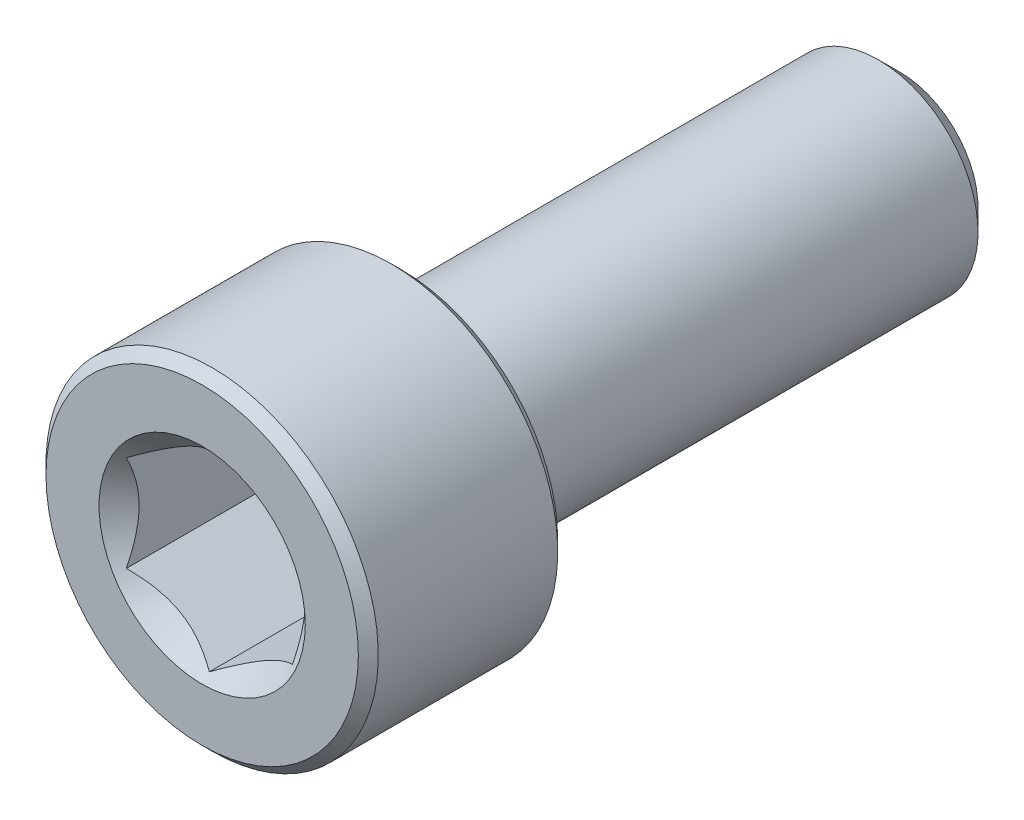
SolidWorks part; units mm, degrees
material "Alloy Steel"
ref_plane "Front Plane" through (0, 0, 0) normal (0, 0, 1) x (1, 0, 0)
ref_plane "Top Plane" through (0, 0, 0) normal (0, 1, 0) x (1, 0, 0)
ref_plane "Right Plane" through (0, 0, 0) normal (1, 0, 0) x (0, 0, -1)
sketch "Sketch1" plane through (0, 0, 0) normal (1, 0, 0) x (0, 0, -1)
  line L0 (-10.5, 0) -> (10.5, 0) construction
  line L1 (10.5, 0) -> (10.5, 2.3505) construction
  line L2 (10.5, 2.3505) -> (9.8505, 3) construction
  line L3 (9.8505, 3) -> (9.75, 3) construction
  line L4 (9.75, 3) -> (-4.5, 3) construction
  line L5 (-4.5, 3) -> (-4.5, 5) construction
  line L6 (-4.5, 5) -> (-10.5, 5) construction
  line L7 (-10.5, 5) -> (-10.5, 0) construction
  line L8 (10.5, 2.3505) -> (10.5, 3) construction
  line L9 (10.4375, 3.1083) -> (10.9375, 2.2422) construction
  line L10 (10.9375, 2.2422) -> (11.4375, 3.1083) construction
  line L11 (11.4375, 3.1083) -> (10.4375, 3.1083) construction
  line L12 (10.9375, 3.1083) -> (10.9375, 3) construction
  line L13 (10.9375, 2.2422) -> (10.9375, 2.3505) construction
  line L14 (10.875, 2.3505) -> (11, 2.3505) construction
  line L15 (10.5, 3) -> (11.375, 3) construction
  line L16 (10.4687, 3.0541) -> (11.4062, 3.0541) construction
  line L17 (10.5, 0) -> (10.5, -3) construction
  line L18 (-4.8, 5) -> (-4.5, 4.7) construction
  line L19 (-10.2, 5) -> (-10.5, 4.7) construction
  line L20 (-4.5, 3) -> (-4.5, 0) construction
  line L21 (-4.5, 1.5) -> (0.5, 1.5) construction
  line L22 (0.5, 1.5) -> (5.5, 1.5) construction
  line L23 (5.5, 1.5) -> (10.5, 1.5) construction
  line L24 (0.5, 1.5) -> (0.5, 3) construction
  line L25 (0.5, 3) -> (0.5, 5) construction
  line L26 (5.5, 1.5) -> (5.5, 5) construction
  point P0 (-10.5, 2.5)
  point P3 (8, 3)
  point P4 (0, 0)
  point P18 (5.5, 3)
  point P22 (10.9375, 2.3505)
  point P24 (9.75, 3)
  point P25 (10.9375, 3)
  point P28 (10.9375, 3.0541)
  point P29 (8, -3)
  point P30 (0.5, 3)
  point P31 (-7.5, 5)
  point P37 (-5.55, 5)
  point P38 (-10.05, 5)
  point P45 (0.5, 1.5)
  point P46 (5.5, 1.5)
  dimension "D2" = 0.125
  dimension "D7" = 0.3
  dimension "D8" = 0.3
  dimension "D9" = 0.3
  dimension "D10" = 0.15
  dimension "D11" = 0.75
  dimension "Drive Size" = 5
  dimension "Head Diameter" = 10
  dimension "Head Height" = 6
  dimension "Thread Pitch" = 1
  dimension "Thread Dia" = 6
  dimension "Length" = 15
  dimension "D12" = 0.75
  dimension "D4" = 2.5
  dimension "D3" = 45
sketch "Sketch2" plane through (0, 0, 0) normal (1, 0, 0) x (0, 0, -1)
  line L0 (-10.5, 0) -> (-10.5, 4.7)
  line L1 (-10.2, 5) -> (-4.8, 5)
  line L2 (-4.5, 4.7) -> (-4.5, 3.3)
  line L4 (9.8505, 3) -> (10.5, 2.3505)
  line L5 (10.5, 2.3505) -> (10.5, 0)
  line L6 (-4.5, 5) -> (-10.5, 5) construction
  line L7 (10.5, 0) -> (-10.5, 0)
  line L8 (-10.2, 5) -> (-10.5, 4.7) construction
  line L10 (-10.2, 5) -> (-10.5, 4.7)
  line L14 (-4.8, 5) -> (-4.5, 4.7) construction
  line L16 (-4.8, 5) -> (-4.5, 4.7)
  line L17 (-4.5, 3) -> (-4.5, 5) construction
  line L19 (-4.2, 3) -> (9.8505, 3)
  line L20 (9.75, 3) -> (-4.5, 3) construction
  arc A1 (-4.5, 3.3) -> (-4.2, 3) centre (-4.2, 3.3) ccw
  dimension "D3" = 0.3
revolve "Revolve1" add sketch "Sketch2" angle 360 about L7
sketch "Sketch3" plane through (0, 0, 10.5) normal (0, 0, 1) x (1, 0, 0)
  line L1 (2.5, -1.4434) -> (2.5, 1.4434)
  line L2 (2.5, 1.4434) -> (0, 2.8868)
  line L3 (0, 2.8868) -> (-2.5, 1.4434)
  line L4 (-2.5, 1.4434) -> (-2.5, -1.4434)
  line L5 (-2.5, -1.4434) -> (0, -2.8868)
  line L6 (0, -2.8868) -> (2.5, -1.4434)
  circle A0 centre (0, 0) radius 2.5 construction
  circle A1 centre (0, 0) radius 5 construction
  circle A2 centre (0, 0) radius 5 construction
  circle A3 centre (0, 0) radius 2.8868 construction
  point P13 (0, 0)
  dimension "D1" = 5.7735
extrude "Cut-Extrude1" cut sketch "Sketch3" against normal offset from surface (5 mm away) 1 up to face at (0, 4.7, 4.5)
sketch "Sketch4" plane through (0, 0, 10.5) normal (0, 0, 1) x (1, 0, 0)
  circle A0 centre (0, 0) radius 3.1033
  dimension "D1" = 6.2065
extrude "Cut-Extrude2" cut sketch "Sketch4" against normal up to vertex (3 mm away) draft 45 up to point (0, 5, 7.5)
sketch "Sketch11" plane through (0, 0, 0) normal (1, 0, 0) x (0, 0, -1)
  line L0 (-10.5, 0) -> (10.5, 0) construction
  line L1 (-10.5, 0) -> (10.5, 0) construction
  line L2 (-1.6875, 0) -> (-1.6875, 3) construction
  line L3 (9.75, 3) -> (-4.5, 3) construction
  line L4 (7.6875, 0) -> (7.6875, 3) construction
  line L6 (10.5, 2.3505) -> (10.5, 3) construction
  point P2 (-1.6875, 0)
  point P3 (7.6875, 0)
  dimension "D1" = 2.8125
  dimension "D2" = 2.8125
sketch "Sketch6" [suppressed] plane through (0, 0, -10.5) normal (0, 0, -1) x (-1, 0, 0)
  circle A0 centre (0, 0) radius 3
curve "Helix/Spiral1" [suppressed] pitch 1 height 16 turns 16
sketch "Sketch10" [suppressed] plane through (0, 0, 0) normal (1, 0, 0) x (0, 0, -1)
  line L0 (-4.2, -5) -> (-4.2, 5)
  line L5 (-10.5, 0) -> (10.5, 0) construction
  line L6 (-4.2, 3) -> (-4.2, -3) construction
  point P3 (-4.2, 0)
split "Split1" [suppressed] bodies to split 106
sketch "Sketch7" [suppressed] plane through (0, 0, 0) normal (1, 0, 0) x (0, 0, -1)
  line L0 (10.4687, 3.0541) -> (11.4062, 3.0541)
  line L1 (11.4062, 3.0541) -> (11, 2.3505)
  line L2 (11, 2.3505) -> (10.875, 2.3505)
  line L3 (10.875, 2.3505) -> (10.4687, 3.0541)
sweep "Cut-Sweep1" [suppressed] cut profiles "Sketch7" path "Helix/Spiral1"
sketch "Sketch8" [suppressed] plane through (0, 0, 0) normal (1, 0, 0) x (0, 0, -1)
  line L0 (-4.5, 0) -> (-4.5, 3)
  line L1 (-4.2, -3) -> (-4.2, 3) construction
  line L2 (-4.5, 3) -> (-4.2, 3)
  line L4 (-4.2, 3) -> (-2.4679, 0)
  line L5 (-2.4679, 0) -> (-4.5, 0)
  line L6 (9.75, 3) -> (-4.5, 3) construction
  line L7 (-10.5, 0) -> (10.5, 0) construction
  dimension "D1" = 60
revolve "Revolve2" [suppressed] add sketch "Sketch8" angle 360 about L5
equation "\"D2@Sketch1\" = \"Thread Pitch@Sketch1\" / 8"
equation "\"D4@Helix/Spiral1\" = \"Thread Pitch@Sketch1\""
equation "\"D7@Sketch1\" = \"Head Height@Sketch1\" * .05"
equation "\"D8@Sketch1\"=\"D7@Sketch1\""
equation "\"D9@Sketch1\"=\"D7@Sketch1\""
equation "\"D10@Sketch1\"=\"D7@Sketch1\"/2"
equation "\"D11@Sketch1\"=\"D10@Sketch1\"*5"
equation "\"D4@Sketch1\"=\"Thread Pitch@Sketch1\"*2.5"
equation "\"D12@Sketch1\"=\"Thread Pitch@Sketch1\"*.75"
equation "\"D3@Helix/Spiral1\"=\"Length@Sketch1\"+\"Thread Pitch@Sketch1\""
equation "\"D3@Sketch2\"=\"Thread Dia@Sketch1\"*0.05"
equation "\"D1@Sketch11\"=\"Length@Sketch1\"*0.1875"
equation "\"D2@Sketch11\"=\"D1@Sketch11\""
equation "\"D1@Sketch4\"=\"D1@Sketch3\"*1.075"
